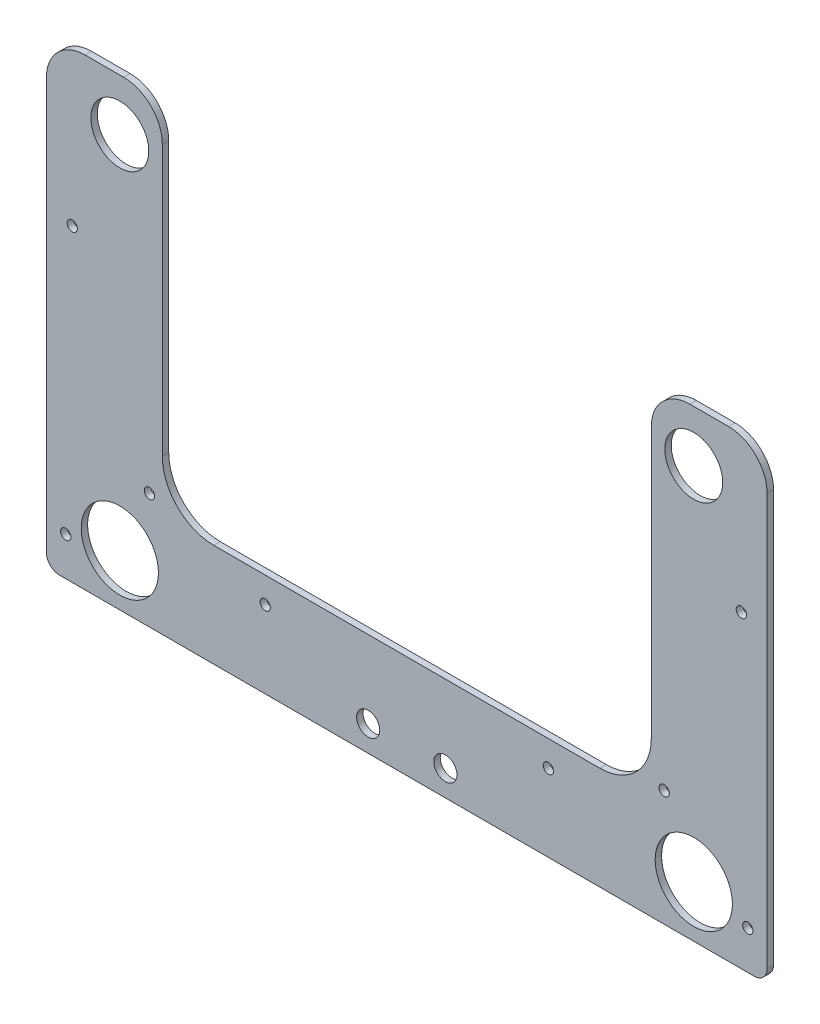
SolidWorks part; units mm, degrees
ref_plane "Front Plane" through (0, 0, 0) normal (0, 0, 1) x (1, 0, 0)
ref_plane "Top Plane" through (0, 0, 0) normal (0, 1, 0) x (1, 0, 0)
ref_plane "Right Plane" through (0, 0, 0) normal (1, 0, 0) x (0, 0, -1)
sketch "Sketch1" plane through (0, 0, 0) normal (0, 0, 1) x (1, 0, 0)
  line L5 (120.65, -152.4) -> (120.65, -6.35)
  line L6 (127, 0) -> (171.45, 0) construction
  line L7 (177.8, -6.35) -> (177.8, -222.25)
  line L10 (0, -206.2199) -> (0, -63.6275) construction
  line L11 (-54.9244, 0) -> (300.6756, 0) construction
  line L13 (12.7, -177.8) -> (95.25, -177.8)
  line L14 (12.7, -228.6) -> (171.45, -228.6)
  line L15 (141.605, -25.4) -> (141.605, -84.2822) construction
  line L16 (141.605, -25.4) -> (141.605, -127) construction
  line L19 (-141.605, -19.05) -> (-141.605, -77.9322) construction
  line L20 (141.605, -25.4) -> (141.605, -203.2) construction
  line L22 (-120.65, -152.4) -> (-120.65, -6.35)
  line L23 (-12.7, -177.8) -> (-95.25, -177.8)
  line L24 (-12.7, -228.6) -> (-171.45, -228.6)
  line L25 (-177.8, -6.35) -> (-177.8, -222.25)
  line L26 (-12.7, -177.8) -> (12.7, -177.8)
  line L27 (-12.7, -228.6) -> (12.7, -228.6)
  line L28 (-177.8, -6.35) -> (-177.8, 6.35)
  line L29 (-165.1, 19.05) -> (-133.35, 19.05)
  line L30 (-120.65, 6.35) -> (-120.65, -6.35)
  line L31 (120.65, 6.35) -> (120.65, -6.35)
  line L32 (177.8, -6.35) -> (177.8, 6.35)
  line L33 (165.1, 19.05) -> (133.35, 19.05)
  arc A0 (95.25, -177.8) -> (120.65, -152.4) centre (95.25, -152.4) ccw
  arc A4 (120.65, -6.35) -> (127, 0) centre (127, -6.35) cw construction
  circle A8 centre (141.605, -25.4) radius 14.2875
  circle A9 centre (141.605, -25.4) radius 38.1 construction
  arc A10 (177.8, -6.35) -> (171.45, 0) centre (171.45, -6.35) ccw construction
  arc A11 (171.45, -228.6) -> (177.8, -222.25) centre (171.45, -222.25) ccw
  arc A14 (141.605, -82.55) -> (120.9214, -78.6758) centre (141.605, -25.4) ccw construction
  arc A15 (-141.605, -82.55) -> (-120.9214, -78.6758) centre (-141.605, -25.4) cw construction
  circle A16 centre (-141.605, -25.4) radius 38.1 construction
  circle A17 centre (-141.605, -25.4) radius 14.2875
  arc A19 (-95.25, -177.8) -> (-120.65, -152.4) centre (-95.25, -152.4) cw
  circle A20 centre (141.605, -127) radius 38.1 construction
  circle A21 centre (-141.605, -127) radius 38.1 construction
  arc A23 (-171.45, -228.6) -> (-177.8, -222.25) centre (-171.45, -222.25) cw
  circle A24 centre (-141.605, -203.2) radius 19.05
  circle A37 centre (141.605, -203.2) radius 19.05
  circle A39 centre (-69.85, -190.5) radius 2.54
  circle A40 centre (69.85, -190.5) radius 2.54
  circle A42 centre (-19.05, -215.9) radius 5.715
  arc A44 (-133.35, 19.05) -> (-120.65, 6.35) centre (-133.35, 6.35) cw
  arc A45 (-177.8, 6.35) -> (-165.1, 19.05) centre (-165.1, 6.35) cw
  arc A46 (133.35, 19.05) -> (120.65, 6.35) centre (133.35, 6.35) ccw
  arc A47 (177.8, 6.35) -> (165.1, 19.05) centre (165.1, 6.35) ccw
  circle A50 centre (-149.225, 6.35) radius 2.54
  circle A53 centre (149.225, 6.35) radius 2.54
  circle A54 centre (-168.275, -209.55) radius 2.54
  circle A56 centre (168.275, -209.55) radius 2.54
  circle A58 centre (-165.1, -76.2) radius 2.54
  circle A59 centre (165.1, -76.2) radius 2.54
  circle A60 centre (-127, -171.45) radius 2.54
  circle A61 centre (127, -171.45) radius 2.54
  circle A62 centre (19.05, -215.9) radius 5.715
  point P2 (177.8, -44.45)
  point P18 (177.8, 0)
  point P23 (177.8, -228.6)
  point P24 (177.8, -228.6)
  point P25 (0, 0)
  point P31 (177.8, 0)
  point P38 (0, 0)
  point P48 (-177.8, 0)
  point P49 (-177.8, -228.6)
  point P51 (-177.8, -44.45)
  point P64 (0, -216.8065)
  point P71 (-19.6145, -215.0791)
  point P72 (0, 0)
  point P75 (0, 0)
  point P78 (-141.605, -203.2)
  dimension "D6" = 25.4
  dimension "D7" = 6.35
  dimension "D8" = 6.35
  dimension "D9" = 177.8
  dimension "D10" = 28.575
  dimension "D12" = 76.2
  dimension "D13" = 57.15
  dimension "D15" = 38.1
  dimension "D18" = 76.2
  dimension "D21" = 5.08
  dimension "D29" = 9.525
  dimension "D32" = 5.08
  dimension "D35" = 11.43
  dimension "D40" = 12.7
  dimension "D43" = 5.08
  dimension "D45" = 12.7
  dimension "D30" = 5.08
  dimension "D41" = 5.08
  dimension "D22" = 6.35
  dimension "D2" = 120.65
  dimension "D3" = 177.8
  dimension "D4" = 228.6
  dimension "D5" = 177.8
  dimension "D11" = 20.955
  dimension "`" = 25.4
  dimension "D14" = 57.15
  dimension "D16" = 184.15
  dimension "D17" = 101.6
  dimension "D19" = 25.4
  dimension "D20" = 107.95
  dimension "D23" = 57.15
  dimension "D25" = 12.7
  dimension "D26" = 19.05
  dimension "D27" = 25.4
  dimension "D28" = 25.4
  dimension "D31" = 19.05
  dimension "D33" = 12.7
  dimension "D34" = 38.1
  dimension "D39" = 19.05
  dimension "D44" = 28.575
  dimension "D24" = 95.25
extrude "Boss-Extrude3" add sketch "Sketch1" along normal blind 3.175
sketch "Sketch2" plane through (0, 0, 3.175) normal (0, 0, 1) x (1, 0, 0)
  line L0 (177.8, -222.25) -> (177.8, 6.35) construction
  line L1 (-177.8, 19.05) -> (177.8, 19.05)
  line L2 (-177.8, 19.05) -> (-177.8, 0)
  line L3 (-177.8, 0) -> (177.8, 0)
  line L4 (177.8, 19.05) -> (177.8, 0)
  line L5 (-177.8, 6.35) -> (-177.8, -222.25) construction
  line L7 (-133.35, 19.05) -> (-165.1, 19.05) construction
  dimension "D1" = 19.05
extrude "Cut-Extrude1" cut sketch "Sketch2" against normal through all
fillet "Fillet1" radius 19.05 4 edges at (177.8, 0, 1.5875) (120.65, 0, 1.5875) (-120.65, 0, 1.5875) (-177.8, 0, 1.5875)
